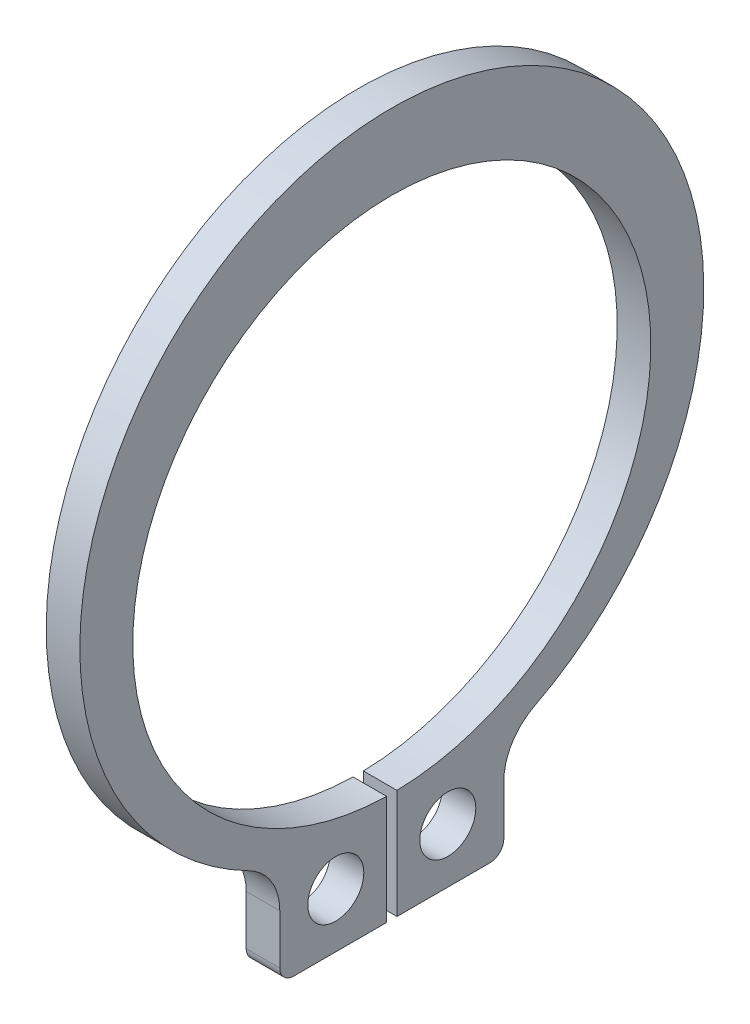
SolidWorks part; units mm, degrees
material "市購件"
ref_plane "前基準面" through (0, 0, 0) normal (0, 0, 1) x (1, 0, 0)
ref_plane "上基準面" through (0, 0, 0) normal (0, 1, 0) x (1, 0, 0)
ref_plane "右基準面" through (0, 0, 0) normal (1, 0, 0) x (0, 0, -1)
sketch "草圖1" plane through (0, 0, 0) normal (1, 0, 0) x (0, 0, -1)
  line L0 (-4, -10.8801) -> (-4, -12.65)
  line L1 (-3.5, -13.15) -> (-0.185, -13.15)
  line L2 (-0.185, -13.15) -> (-0.185, -9.2481)
  line L3 (0.185, -9.2481) -> (0.185, -13.15)
  line L4 (0.185, -13.15) -> (3.5, -13.15)
  line L5 (4, -12.65) -> (4, -10.8801)
  arc A0 (5.0868, -9.1008) -> (-5.0868, -9.1008) centre (0, 0.81) ccw
  arc A1 (-5.0868, -9.1008) -> (-4, -10.8801) centre (-6, -10.8801) cw
  arc A2 (-4, -12.65) -> (-3.5, -13.15) centre (-3.5, -12.65) ccw
  arc A3 (-0.185, -9.2481) -> (0.185, -9.2481) centre (0, 0) cw
  arc A4 (3.5, -13.15) -> (4, -12.65) centre (3.5, -12.65) ccw
  arc A5 (4, -10.8801) -> (5.0868, -9.1008) centre (6, -10.8801) cw
  circle A6 centre (2, -11.2) radius 1
  circle A7 centre (-2, -11.2) radius 1
extrude "填料-伸長1" add sketch "草圖1" against normal blind 0.6 and the other way blind 0.6
ref_plane "平面1" through (0.6, 0, 0) normal (1, 0, 0) x (0, 0, -1)
ref_plane "1 XY" through (0, 0, 0) normal (1, 0, 0) x (0, 0, -1)
ref_plane "1 XZ" through (0, 0, 0) normal (0, -1, 0) x (-1, 0, 0)
ref_plane "1 YZ" through (0, 0, 0) normal (0, 0, -1) x (-1, 0, 0)
ref_axis "1 X" through (0, 0, 80.9) along (0, 0, -1)
ref_axis "1 Y" through (0, -50, 0) along (0, 1, 0)
ref_axis "1 Z" through (80.9, 0, 0) along (-1, 0, 0)
sketch3d "1"
  point P0 (0, 0, 0)
ref_plane "combination module XY" through (0.6, 0, 0) normal (1, 0, 0) x (0, 0, -1)
ref_plane "combination module XZ" through (0, 0, 0) normal (0, -1, 0) x (-1, 0, 0)
ref_plane "combination module YZ" through (0, 0, 0) normal (0, 0, -1) x (-1, 0, 0)
ref_axis "combination module X" through (0.6, 0, 80.9) along (0, 0, -1)
ref_axis "combination module Y" through (0.6, -50, 0) along (0, 1, 0)
ref_axis "combination module Z" through (80.9, 0, 0) along (-1, 0, 0)
sketch3d "combination module"
  point P0 (0.6, 0, 0)
